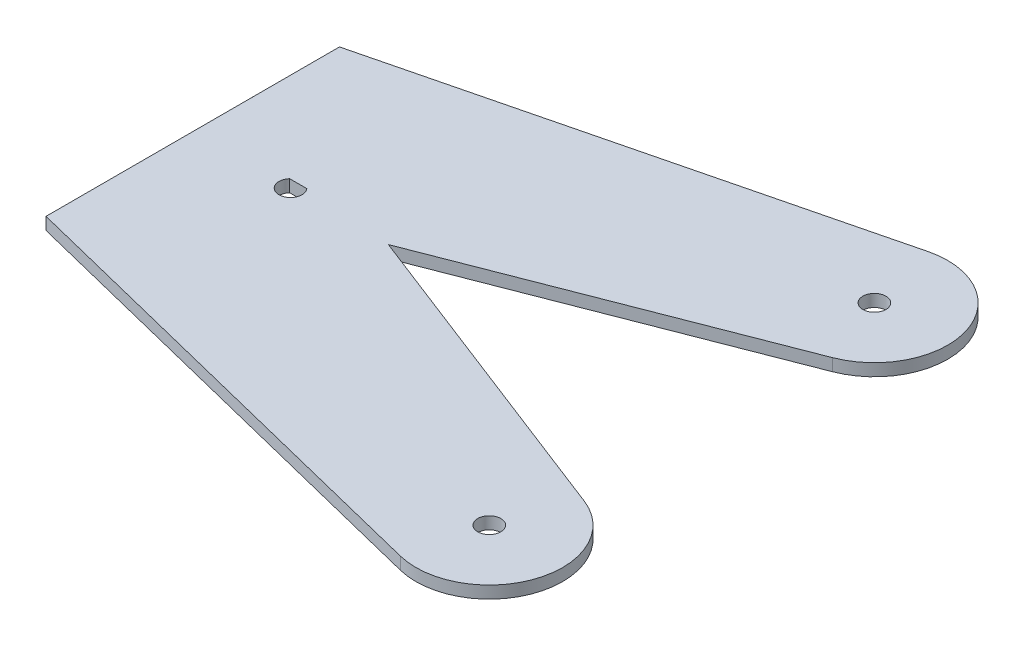
SolidWorks part; units mm, degrees
ref_plane "Front Plane" through (0, 0, 0) normal (0, 0, 1) x (1, 0, 0)
ref_plane "Top Plane" through (0, 0, 0) normal (0, 1, 0) x (1, 0, 0)
ref_plane "Right Plane" through (0, 0, 0) normal (1, 0, 0) x (0, 0, -1)
sketch "Sketch1" plane through (0, 0, 0) normal (0, 1, 0) x (1, 0, 0)
  line L0 (-25.4, 38.1) -> (97.0101, 68.4888)
  line L1 (-25.4, 38.1) -> (-25.4, -38.1)
  line L2 (-25.4, -38.1) -> (97.0101, -68.4888)
  line L3 (108.491, -32.24) -> (25.4, 0)
  line L5 (25.4, 0) -> (108.491, 32.24)
  line L6 (101.6, -50) -> (101.6, 50) construction
  line L7 (-2.2361, 2) -> (2.2361, 2)
  arc A0 (108.491, -32.24) -> (97.0101, -68.4888) centre (101.6, -50) cw
  arc A1 (97.0101, 68.4888) -> (108.491, 32.24) centre (101.6, 50) cw
  arc A2 (2.2361, 2) -> (-2.2361, 2) centre (0, 0) cw
  circle A3 centre (101.6, 50) radius 3
  circle A4 centre (101.6, -50) radius 3
  point P8 (-25.4, 0)
  point P12 (101.6, 0)
  dimension "D1" = 19.05
  dimension "D7" = 3
  dimension "D9" = 6
  dimension "D2" = 76.2
  dimension "D3" = 25.4
  dimension "D4" = 101.6
  dimension "D5" = 100
  dimension "D6" = 25.4
  dimension "D8" = 2
extrude "Boss-Extrude1" add sketch "Sketch1" along normal mid plane 3.175
